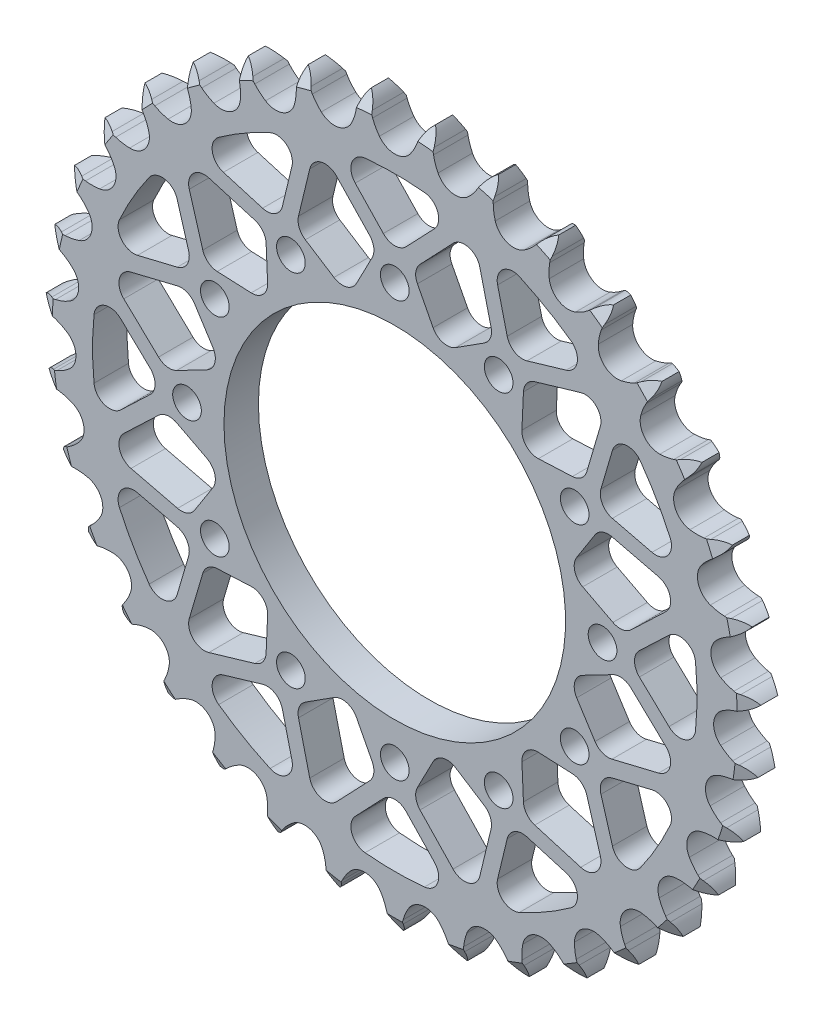
SolidWorks part; units mm, degrees
material "7075-T6 (SN)"
ref_plane "Front Plane" through (0, 0, 0) normal (0, 0, 1) x (1, 0, 0)
ref_plane "Top Plane" through (0, 0, 0) normal (0, 1, 0) x (1, 0, 0)
ref_plane "Right Plane" through (0, 0, 0) normal (1, 0, 0) x (0, 0, -1)
sketch "Work Sketch" plane through (0, 0, 0) normal (0, 0, 1) x (1, 0, 0)
  line L0 (0, 0) -> (0, 160.4542) construction
  line L1 (-112.0919, 70.8395) -> (87.2579, 70.8395) construction
  line L2 (5.0903, 120.8822) -> (5.0903, 112.9699) construction
  line L3 (-12.8497, 74.6356) -> (16.7256, 74.6356) construction
  line L4 (5.0903, 74.6356) -> (-6.074, 66.3097) construction
  line L5 (5.0903, 74.6356) -> (-4.641, 71.0332) construction
  line L6 (-4.641, 71.0332) -> (-6.9559, 77.2865)
  line L7 (-11.5114, 69.8433) -> (-7.1525, 69.8433) construction
  line L8 (-11.0678, 124.7602) -> (-11.0678, 110.2345) construction
  line L9 (0, 0) -> (-3.8324, 42.5811) construction
  circle A0 centre (0, 0) radius 70.8395
  circle A1 centre (0, 70.8395) radius 4.0088
  arc A2 (-4.641, 71.0332) -> (-3.2136, 68.4429) centre (5.0682, 74.6949) ccw
  circle A3 centre (-11.0678, 69.8433) radius 6.4401
  point P23 (-3.2136, 68.4429)
  dimension "D1" = 141.6789
  dimension "D8" = 10.3767
  dimension "D2" = 8.0177
  dimension "D3" = 5.0903
  dimension "D4" = 3.7962
  dimension "D5" = 36.714
  dimension "D6" = 16.4
  dimension "D7" = 10.3767
  dimension "D9" = 0.9961
  dimension "D10" = 11.0678
  dimension "D11" = 5.143
sketch "Teeth Sketch" plane through (0, 0, 0) normal (0, 0, 1) x (1, 0, 0)
  line L0 (5.0282, 72.0792) -> (4.641, 71.0332)
  line L1 (-8.3399, 92.6643) -> (-5.3292, 59.2127) construction
  line L2 (0, 0) -> (-12.1309, 132.2) construction
  line L3 (7.9229, 71.8186) -> (8.1171, 70.7203)
  line L4 (17927.8618, -199194.8588) -> (-17931.6941, 199237.4399) construction
  line L5 (0, 146.3285) -> (0, 56.9858) construction
  line L6 (17.8176, 70.023) -> (17.2498, 69.063)
  line L7 (0, -200000) -> (0, 200160.4542) construction
  line L8 (20.6192, 69.2498) -> (20.6142, 68.1345)
  line L9 (-4.641, 71.0332) -> (-6.9559, 77.2865) construction
  line L10 (43.6371, 57.589) -> (43.2405, 56.5465)
  line L11 (-5.0282, 72.0792) -> (-4.641, 71.0332)
  line L12 (30.0344, 65.7163) -> (29.3043, 64.873)
  line L13 (32.6529, 64.4552) -> (32.4488, 63.3587)
  line L14 (41.2858, 59.2973) -> (40.4169, 58.598)
  line L15 (51.2103, 50.9725) -> (50.2305, 50.4396)
  line L16 (53.2187, 48.8718) -> (52.6424, 47.9169)
  line L17 (59.4888, 41.0094) -> (58.4296, 40.66)
  line L18 (61.0899, 38.5838) -> (60.3523, 37.7472)
  line L19 (65.8553, 29.7283) -> (64.7507, 29.5736)
  line L20 (66.9976, 27.0558) -> (66.1224, 26.3643)
  line L21 (70.1052, 17.4916) -> (68.9907, 17.5366)
  line L22 (70.7519, 14.6581) -> (69.7673, 14.134)
  line L23 (72.1018, 4.6927) -> (71.0133, 4.9361)
  line L24 (72.2322, 1.7893) -> (71.1699, 1.4494)
  line L25 (71.781, -8.2569) -> (70.7534, -7.8232)
  line L26 (71.3909, -11.137) -> (70.2849, -11.2818)
  line L27 (69.1531, -20.9412) -> (68.2195, -20.331)
  line L28 (68.255, -23.7054) -> (67.141, -23.6503)
  line L29 (64.3026, -32.9525) -> (63.493, -32.1853)
  line L30 (62.9254, -35.5118) -> (61.8391, -35.2587)
  line L31 (57.3853, -43.9046) -> (56.7257, -43.0052)
  line L32 (55.5732, -46.1769) -> (54.5496, -45.7339)
  line L33 (48.6237, -53.4456) -> (48.1352, -52.4428)
  line L34 (46.435, -55.3578) -> (45.5069, -54.7392)
  line L35 (38.2992, -61.2688) -> (37.9976, -60.1949)
  line L36 (35.8042, -62.7594) -> (35.0015, -61.985)
  line L37 (26.7437, -67.1227) -> (26.6388, -66.0123)
  line L38 (24.0227, -68.144) -> (23.3712, -67.2387)
  line L39 (14.3287, -70.8193) -> (14.4237, -69.708)
  line L40 (11.4691, -71.3383) -> (10.9896, -70.3312)
  line L41 (1.4532, -72.2397) -> (1.7451, -71.1632)
  line L42 (-1.4532, -72.2397) -> (-1.7451, -71.1632)
  line L43 (-11.4691, -71.3383) -> (-10.9896, -70.3312)
  line L44 (-14.3287, -70.8193) -> (-14.4237, -69.708)
  line L45 (-24.0227, -68.144) -> (-23.3712, -67.2387)
  line L46 (-26.7437, -67.1227) -> (-26.6388, -66.0123)
  line L47 (-35.8042, -62.7594) -> (-35.0015, -61.985)
  line L48 (-38.2992, -61.2688) -> (-37.9976, -60.1949)
  line L49 (-46.435, -55.3578) -> (-45.5069, -54.7392)
  line L50 (-48.6237, -53.4456) -> (-48.1352, -52.4428)
  line L51 (-55.5732, -46.1769) -> (-54.5496, -45.7339)
  line L52 (-57.3853, -43.9046) -> (-56.7257, -43.0052)
  line L53 (-62.9254, -35.5118) -> (-61.8391, -35.2587)
  line L54 (-64.3026, -32.9525) -> (-63.493, -32.1853)
  line L55 (-68.255, -23.7054) -> (-67.141, -23.6503)
  line L56 (-69.1531, -20.9412) -> (-68.2195, -20.331)
  line L57 (-71.3909, -11.137) -> (-70.2849, -11.2818)
  line L58 (-71.781, -8.2569) -> (-70.7534, -7.8232)
  line L59 (-72.2322, 1.7893) -> (-71.1699, 1.4494)
  line L60 (-72.1018, 4.6927) -> (-71.0133, 4.9361)
  line L61 (-70.7519, 14.6581) -> (-69.7673, 14.134)
  line L62 (-70.1052, 17.4916) -> (-68.9907, 17.5366)
  line L63 (-66.9976, 27.0558) -> (-66.1224, 26.3643)
  line L64 (-65.8553, 29.7283) -> (-64.7507, 29.5736)
  line L65 (-61.0899, 38.5838) -> (-60.3523, 37.7472)
  line L66 (-59.4888, 41.0094) -> (-58.4296, 40.66)
  line L67 (-53.2187, 48.8718) -> (-52.6424, 47.9169)
  line L68 (-51.2103, 50.9725) -> (-50.2305, 50.4396)
  line L69 (-43.6371, 57.589) -> (-43.2405, 56.5465)
  line L70 (-41.2858, 59.2973) -> (-40.4169, 58.598)
  line L71 (-32.6529, 64.4552) -> (-32.4488, 63.3587)
  line L72 (-30.0344, 65.7163) -> (-29.3043, 64.873)
  line L73 (-20.6192, 69.2498) -> (-20.6142, 68.1345)
  line L74 (-17.8176, 70.023) -> (-17.2498, 69.063)
  line L75 (-7.9229, 71.8186) -> (-8.1171, 70.7203)
  arc A0 (-6.856, 74.7153) -> (-5.0282, 72.0792) centre (-11.0678, 69.8433) cw
  circle A1 centre (-11.0678, 69.8433) radius 6.4401 construction
  arc A2 (-3.2136, 68.4429) -> (-4.641, 71.0332) centre (5.0682, 74.6949) cw
  arc A3 (-4.641, 71.0332) -> (-3.2136, 68.4429) centre (5.0682, 74.6949) ccw construction
  circle A4 centre (0, 70.8395) radius 4.0088 construction
  arc A5 (-3.2136, 68.4429) -> (3.2136, 68.4429) centre (0, 70.8395) ccw
  arc A6 (3.2136, 68.4429) -> (4.641, 71.0332) centre (-5.0682, 74.6949) ccw
  arc A7 (6.856, 74.7153) -> (5.0282, 72.0792) centre (11.0678, 69.8433) ccw
  arc A8 (6.5951, 74.7388) -> (7.9229, 71.8186) centre (1.5811, 70.6972) cw
  arc A9 (9.059, 67.9168) -> (8.1171, 70.7203) centre (18.324, 72.5896) cw
  arc A10 (9.059, 67.9168) -> (15.3829, 66.7692) centre (12.6489, 69.701) ccw
  arc A11 (15.3829, 66.7692) -> (17.2498, 69.063) centre (8.3506, 74.3995) ccw
  arc A12 (20.0867, 72.2905) -> (17.8176, 70.023) centre (23.3609, 66.7447) ccw
  arc A13 (19.8343, 72.3601) -> (20.6192, 69.2498) centre (14.1792, 69.2787) cw
  arc A14 (21.0404, 65.2078) -> (20.6142, 68.1345) centre (30.9909, 68.1512) cw
  arc A15 (21.0404, 65.2078) -> (27.0578, 62.9494) centre (24.8912, 66.3224) ccw
  arc A16 (27.0578, 62.9494) -> (29.3043, 64.873) centre (21.5009, 71.7128) ccw
  arc A17 (32.6719, 67.5421) -> (30.0344, 65.7163) centre (34.9032, 61.5008) ccw
  arc A18 (32.4359, 67.6557) -> (32.6529, 64.4552) centre (26.3215, 65.6336) cw
  arc A19 (32.3456, 60.403) -> (32.4488, 63.3587) centre (42.6617, 61.5223) cw
  arc A20 (32.3456, 60.403) -> (37.863, 57.1065) centre (36.3335, 60.812) ccw
  arc A21 (37.863, 57.1065) -> (40.4169, 58.598) centre (33.9602, 66.7212) ccw
  arc A22 (44.207, 60.6229) -> (41.2858, 59.2973) centre (45.3237, 54.2803) ccw
  arc A23 (43.9951, 60.7768) -> (43.6371, 57.589) centre (37.6178, 59.8789) cw
  arc A24 (42.6112, 53.6567) -> (43.2405, 56.5465) centre (52.9614, 52.9161) cw
  arc A25 (42.6112, 53.6567) -> (47.4513, 49.428) centre (46.608, 53.3472) ccw
  arc A26 (47.4513, 49.428) -> (50.2305, 50.4396) centre (45.328, 59.5852) ccw
  arc A27 (54.3212, 51.7552) -> (51.2103, 50.9725) centre (54.2875, 45.3151) ccw
  arc A28 (54.1402, 51.9445) -> (53.2187, 48.8718) centre (47.7051, 52.1997) cw
  arc A29 (51.5072, 45.1859) -> (52.6424, 47.9169) centre (61.5588, 42.6091) cw
  arc A30 (51.5072, 45.1859) -> (55.5144, 40.161) centre (55.3845, 44.1677) ccw
  arc A31 (55.5144, 40.161) -> (58.4296, 40.66) centre (55.2389, 50.534) ccw
  arc A32 (62.6894, 41.224) -> (59.4888, 41.0094) centre (61.5064, 34.8935) ccw
  arc A33 (62.5452, 41.4426) -> (61.0899, 38.5838) centre (56.2591, 42.8428) cw
  arc A34 (58.7477, 35.2628) -> (60.3523, 37.7472) centre (68.1777, 30.9326) cw
  arc A35 (58.7477, 35.2628) -> (61.7933, 29.6031) centre (62.3809, 33.5686) ccw
  arc A36 (61.7933, 29.6031) -> (64.7507, 29.5736) centre (63.3744, 39.8586) ccw
  arc A37 (69.0428, 29.3679) -> (65.8553, 29.7283) centre (66.7484, 23.3503) ccw
  arc A38 (68.9399, 29.6087) -> (66.9976, 27.0558) centre (63.0048, 32.1088) cw
  arc A39 (64.1, 24.2063) -> (66.1224, 26.3643) centre (72.6052, 18.2619) cw
  arc A40 (64.1, 24.2063) -> (66.0861, 18.0937) centre (67.3723, 21.8906) ccw
  arc A41 (66.0861, 18.0937) -> (68.9907, 17.5366) centre (69.4729, 27.9021) ccw
  arc A42 (73.1771, 16.5679) -> (70.1052, 17.4916) centre (69.8451, 11.0567) ccw
  arc A43 (73.1188, 16.8232) -> (70.7519, 14.6581) centre (67.7256, 20.3429) cw
  arc A44 (67.3921, 12.3718) -> (69.7673, 14.134) centre (74.6992, 5.0042) cw
  arc A45 (67.3921, 12.3718) -> (68.2548, 6.0028) centre (70.1983, 9.509) ccw
  arc A46 (68.2548, 6.0028) -> (71.0133, 4.9361) centre (73.3386, 15.0489) ccw
  arc A47 (74.9595, 3.2354) -> (72.1018, 4.6927) centre (70.6969, -1.5923) ccw
  arc A48 (74.9477, 3.497) -> (72.2322, 1.7893) centre (70.2696, 7.9231) cw
  arc A49 (68.5181, 0.1397) -> (71.1699, 1.4494) centre (74.3923, -8.4143) cw
  arc A50 (68.5181, 0.1397) -> (68.2298, -6.281) centre (70.7681, -3.1782) ccw
  arc A51 (68.2298, -6.281) -> (70.7534, -7.8232) centre (74.8471, 1.7119) ccw
  arc A52 (74.3325, -10.2012) -> (71.781, -8.2569) centre (69.2765, -14.1901) ccw
  arc A53 (74.3677, -9.9416) -> (71.3909, -11.137) centre (70.555, -4.7513) cw
  arc A54 (67.442, -12.097) -> (70.2849, -11.2818) centre (71.6944, -21.5623) cw
  arc A55 (67.442, -12.097) -> (66.0118, -18.363) centre (69.0634, -15.7633) ccw
  arc A56 (66.0118, -18.363) -> (68.2195, -20.331) centre (73.9499, -11.6801) ccw
  arc A57 (71.3165, -23.3098) -> (69.1531, -20.9412) centre (65.6294, -26.3319) ccw
  arc A58 (71.3974, -23.0607) -> (68.255, -23.7054) centre (68.5728, -17.2731) cw
  arc A59 (64.1981, -23.9448) -> (67.141, -23.6503) centre (66.6921, -34.0173) cw
  arc A60 (64.1981, -23.9448) -> (61.6721, -29.8547) centre (65.1388, -27.8417) ccw
  arc A61 (61.6721, -29.8547) -> (63.493, -32.1853) centre (70.676, -24.6966) ccw
  arc A62 (66.0083, -35.6693) -> (64.3026, -32.9525) centre (59.873, -37.6273) ccw
  arc A63 (66.1324, -35.4386) -> (62.9254, -35.5118) centre (64.3866, -29.2396) cw
  arc A64 (58.8909, -35.023) -> (61.8391, -35.2587) centre (59.5463, -45.379) cw
  arc A65 (58.8909, -35.023) -> (55.3502, -40.3869) centre (59.1207, -39.0252) ccw
  arc A66 (55.3502, -40.3869) -> (56.7257, -43.0052) centre (65.1304, -36.9194) ccw
  arc A67 (58.5785, -46.8823) -> (57.3853, -43.9046) centre (52.1922, -47.7133) ccw
  arc A68 (58.7418, -46.6775) -> (55.5732, -46.1769) centre (58.1309, -40.2664) cw
  arc A69 (51.6909, -44.9755) -> (54.5496, -45.7339) centre (50.4867, -55.2821) cw
  arc A70 (51.6909, -44.9755) -> (47.2494, -49.6211) centre (51.2024, -48.9545) ccw
  arc A71 (47.2494, -49.6211) -> (48.1352, -52.4428) centre (57.4915, -47.9556) ccw
  arc A72 (49.266, -56.5885) -> (48.6237, -53.4456) centre (42.8339, -56.2658) ccw
  arc A73 (49.4632, -56.4161) -> (46.435, -55.3578) centre (50.0069, -49.999) cw
  arc A74 (42.8296, -53.4825) -> (45.5069, -54.7392) centre (39.8043, -63.4085) cw
  arc A75 (42.8296, -53.4825) -> (37.6299, -57.2603) centre (41.6384, -57.3103) ccw
  arc A76 (37.6299, -57.2603) -> (37.9976, -60.1949) centre (48.0048, -57.4505) ccw
  arc A77 (38.37, -64.4758) -> (38.2992, -61.2688) centre (32.0989, -63.0099) ccw
  arc A78 (38.5948, -64.3415) -> (35.8042, -62.7594) centre (40.2756, -58.1246) cw
  arc A79 (32.5916, -60.2706) -> (35.0015, -61.985) centre (27.8426, -69.4968) cw
  arc A80 (32.5916, -60.2706) -> (26.8009, -63.0592) centre (30.7361, -63.8241) ccw
  arc A81 (26.8009, -63.0592) -> (26.6388, -66.0123) centre (36.9752, -65.0988) ccw
  arc A82 (26.2407, -70.2909) -> (26.7437, -67.1227) centre (20.3322, -67.7288) ccw
  arc A83 (26.4859, -70.1989) -> (24.0227, -68.144) centre (29.2498, -64.382) cw
  arc A84 (21.3061, -65.1215) -> (23.3712, -67.2387) centre (14.9861, -73.3515) cw
  arc A85 (21.3061, -65.1215) -> (15.1105, -66.8313) centre (18.8459, -68.2866) ccw
  arc A86 (15.1105, -66.8313) -> (14.4237, -69.708) centre (24.7571, -70.6548) ccw
  arc A87 (13.2681, -73.8468) -> (14.3287, -70.8193) centre (7.912, -70.2708) ccw
  arc A88 (13.5258, -73.8) -> (11.4691, -71.3383) centre (17.2839, -68.5701) cw
  arc A89 (9.3358, -67.8793) -> (10.9896, -70.3312) centre (1.6478, -74.8485) cw
  arc A90 (9.3358, -67.8793) -> (2.9345, -68.4554) centre (6.35, -70.5543) ccw
  arc A91 (2.9345, -68.4554) -> (1.7451, -71.1632) centre (11.7434, -73.9399) ccw
  arc A92 (-0.131, -75.0291) -> (1.4532, -72.2397) centre (-4.7625, -70.5543) ccw
  arc A93 (0.131, -75.0291) -> (-1.4532, -72.2397) centre (4.7625, -70.5543) cw
  arc A94 (-2.9345, -68.4554) -> (-1.7451, -71.1632) centre (-11.7434, -73.9399) cw
  arc A95 (-2.9345, -68.4554) -> (-9.3358, -67.8793) centre (-6.35, -70.5543) ccw
  arc A96 (-9.3358, -67.8793) -> (-10.9896, -70.3312) centre (-1.6478, -74.8485) ccw
  arc A97 (-13.5258, -73.8) -> (-11.4691, -71.3383) centre (-17.2839, -68.5701) ccw
  arc A98 (-13.2681, -73.8468) -> (-14.3287, -70.8193) centre (-7.912, -70.2708) cw
  arc A99 (-15.1105, -66.8313) -> (-14.4237, -69.708) centre (-24.7571, -70.6548) cw
  arc A100 (-15.1105, -66.8313) -> (-21.3061, -65.1215) centre (-18.8459, -68.2866) ccw
  arc A101 (-21.3061, -65.1215) -> (-23.3712, -67.2387) centre (-14.9861, -73.3515) ccw
  arc A102 (-26.4859, -70.1989) -> (-24.0227, -68.144) centre (-29.2498, -64.382) ccw
  arc A103 (-26.2407, -70.2909) -> (-26.7437, -67.1227) centre (-20.3322, -67.7288) cw
  arc A104 (-26.8009, -63.0592) -> (-26.6388, -66.0123) centre (-36.9752, -65.0988) cw
  arc A105 (-26.8009, -63.0592) -> (-32.5916, -60.2706) centre (-30.7361, -63.8241) ccw
  arc A106 (-32.5916, -60.2706) -> (-35.0015, -61.985) centre (-27.8426, -69.4968) ccw
  arc A107 (-38.5948, -64.3415) -> (-35.8042, -62.7594) centre (-40.2756, -58.1246) ccw
  arc A108 (-38.37, -64.4758) -> (-38.2992, -61.2688) centre (-32.0989, -63.0099) cw
  arc A109 (-37.6299, -57.2603) -> (-37.9976, -60.1949) centre (-48.0048, -57.4505) cw
  arc A110 (-37.6299, -57.2603) -> (-42.8296, -53.4825) centre (-41.6384, -57.3103) ccw
  arc A111 (-42.8296, -53.4825) -> (-45.5069, -54.7392) centre (-39.8043, -63.4085) ccw
  arc A112 (-49.4632, -56.4161) -> (-46.435, -55.3578) centre (-50.0069, -49.999) ccw
  arc A113 (-49.266, -56.5885) -> (-48.6237, -53.4456) centre (-42.8339, -56.2658) cw
  arc A114 (-47.2494, -49.6211) -> (-48.1352, -52.4428) centre (-57.4915, -47.9556) cw
  arc A115 (-47.2494, -49.6211) -> (-51.6909, -44.9755) centre (-51.2024, -48.9545) ccw
  arc A116 (-51.6909, -44.9755) -> (-54.5496, -45.7339) centre (-50.4867, -55.2821) ccw
  arc A117 (-58.7418, -46.6775) -> (-55.5732, -46.1769) centre (-58.1309, -40.2664) ccw
  arc A118 (-58.5785, -46.8823) -> (-57.3853, -43.9046) centre (-52.1922, -47.7133) cw
  arc A119 (-55.3502, -40.3869) -> (-56.7257, -43.0052) centre (-65.1304, -36.9194) cw
  arc A120 (-55.3502, -40.3869) -> (-58.8909, -35.023) centre (-59.1207, -39.0252) ccw
  arc A121 (-58.8909, -35.023) -> (-61.8391, -35.2587) centre (-59.5463, -45.379) ccw
  arc A122 (-66.1324, -35.4386) -> (-62.9254, -35.5118) centre (-64.3866, -29.2396) ccw
  arc A123 (-66.0083, -35.6693) -> (-64.3026, -32.9525) centre (-59.873, -37.6273) cw
  arc A124 (-61.6721, -29.8547) -> (-63.493, -32.1853) centre (-70.676, -24.6966) cw
  arc A125 (-61.6721, -29.8547) -> (-64.1981, -23.9448) centre (-65.1388, -27.8417) ccw
  arc A126 (-64.1981, -23.9448) -> (-67.141, -23.6503) centre (-66.6921, -34.0173) ccw
  arc A127 (-71.3974, -23.0607) -> (-68.255, -23.7054) centre (-68.5728, -17.2731) ccw
  arc A128 (-71.3165, -23.3098) -> (-69.1531, -20.9412) centre (-65.6294, -26.3319) cw
  arc A129 (-66.0118, -18.363) -> (-68.2195, -20.331) centre (-73.9499, -11.6801) cw
  arc A130 (-66.0118, -18.363) -> (-67.442, -12.097) centre (-69.0634, -15.7633) ccw
  arc A131 (-67.442, -12.097) -> (-70.2849, -11.2818) centre (-71.6944, -21.5623) ccw
  arc A132 (-74.3677, -9.9416) -> (-71.3909, -11.137) centre (-70.555, -4.7513) ccw
  arc A133 (-74.3325, -10.2012) -> (-71.781, -8.2569) centre (-69.2765, -14.1901) cw
  arc A134 (-68.2298, -6.281) -> (-70.7534, -7.8232) centre (-74.8471, 1.7119) cw
  arc A135 (-68.2298, -6.281) -> (-68.5181, 0.1397) centre (-70.7681, -3.1782) ccw
  arc A136 (-68.5181, 0.1397) -> (-71.1699, 1.4494) centre (-74.3923, -8.4143) ccw
  arc A137 (-74.9477, 3.497) -> (-72.2322, 1.7893) centre (-70.2696, 7.9231) ccw
  arc A138 (-74.9595, 3.2354) -> (-72.1018, 4.6927) centre (-70.6969, -1.5923) cw
  arc A139 (-68.2548, 6.0028) -> (-71.0133, 4.9361) centre (-73.3386, 15.0489) cw
  arc A140 (-68.2548, 6.0028) -> (-67.3921, 12.3718) centre (-70.1983, 9.509) ccw
  arc A141 (-67.3921, 12.3718) -> (-69.7673, 14.134) centre (-74.6992, 5.0042) ccw
  arc A142 (-73.1188, 16.8232) -> (-70.7519, 14.6581) centre (-67.7256, 20.3429) ccw
  arc A143 (-73.1771, 16.5679) -> (-70.1052, 17.4916) centre (-69.8451, 11.0567) cw
  arc A144 (-66.0861, 18.0937) -> (-68.9907, 17.5366) centre (-69.4729, 27.9021) cw
  arc A145 (-66.0861, 18.0937) -> (-64.1, 24.2063) centre (-67.3723, 21.8906) ccw
  arc A146 (-64.1, 24.2063) -> (-66.1224, 26.3643) centre (-72.6052, 18.2619) ccw
  arc A147 (-68.9399, 29.6087) -> (-66.9976, 27.0558) centre (-63.0048, 32.1088) ccw
  arc A148 (-69.0428, 29.3679) -> (-65.8553, 29.7283) centre (-66.7484, 23.3503) cw
  arc A149 (-61.7933, 29.6031) -> (-64.7507, 29.5736) centre (-63.3744, 39.8586) cw
  arc A150 (-61.7933, 29.6031) -> (-58.7477, 35.2628) centre (-62.3809, 33.5686) ccw
  arc A151 (-58.7477, 35.2628) -> (-60.3523, 37.7472) centre (-68.1777, 30.9326) ccw
  arc A152 (-62.5452, 41.4426) -> (-61.0899, 38.5838) centre (-56.2591, 42.8428) ccw
  arc A153 (-62.6894, 41.224) -> (-59.4888, 41.0094) centre (-61.5064, 34.8935) cw
  arc A154 (-55.5144, 40.161) -> (-58.4296, 40.66) centre (-55.2389, 50.534) cw
  arc A155 (-55.5144, 40.161) -> (-51.5072, 45.1859) centre (-55.3845, 44.1677) ccw
  arc A156 (-51.5072, 45.1859) -> (-52.6424, 47.9169) centre (-61.5588, 42.6091) ccw
  arc A157 (-54.1402, 51.9445) -> (-53.2187, 48.8718) centre (-47.7051, 52.1997) ccw
  arc A158 (-54.3212, 51.7552) -> (-51.2103, 50.9725) centre (-54.2875, 45.3151) cw
  arc A159 (-47.4513, 49.428) -> (-50.2305, 50.4396) centre (-45.328, 59.5852) cw
  arc A160 (-47.4513, 49.428) -> (-42.6112, 53.6567) centre (-46.608, 53.3472) ccw
  arc A161 (-42.6112, 53.6567) -> (-43.2405, 56.5465) centre (-52.9614, 52.9161) ccw
  arc A162 (-43.9951, 60.7768) -> (-43.6371, 57.589) centre (-37.6178, 59.8789) ccw
  arc A163 (-44.207, 60.6229) -> (-41.2858, 59.2973) centre (-45.3237, 54.2803) cw
  arc A164 (-37.863, 57.1065) -> (-40.4169, 58.598) centre (-33.9602, 66.7212) cw
  arc A165 (-37.863, 57.1065) -> (-32.3456, 60.403) centre (-36.3335, 60.812) ccw
  arc A166 (-32.3456, 60.403) -> (-32.4488, 63.3587) centre (-42.6617, 61.5223) ccw
  arc A167 (-32.4359, 67.6557) -> (-32.6529, 64.4552) centre (-26.3215, 65.6336) ccw
  arc A168 (-32.6719, 67.5421) -> (-30.0344, 65.7163) centre (-34.9032, 61.5008) cw
  arc A169 (-27.0578, 62.9494) -> (-29.3043, 64.873) centre (-21.5009, 71.7128) cw
  arc A170 (-27.0578, 62.9494) -> (-21.0404, 65.2078) centre (-24.8912, 66.3224) ccw
  arc A171 (-21.0404, 65.2078) -> (-20.6142, 68.1345) centre (-30.9909, 68.1512) ccw
  arc A172 (-19.8343, 72.3601) -> (-20.6192, 69.2498) centre (-14.1792, 69.2787) ccw
  arc A173 (-20.0867, 72.2905) -> (-17.8176, 70.023) centre (-23.3609, 66.7447) cw
  arc A174 (-15.3829, 66.7692) -> (-17.2498, 69.063) centre (-8.3506, 74.3995) cw
  arc A175 (-15.3829, 66.7692) -> (-9.059, 67.9168) centre (-12.6489, 69.701) ccw
  arc A176 (-9.059, 67.9168) -> (-8.1171, 70.7203) centre (-18.324, 72.5896) ccw
  arc A177 (-6.5951, 74.7388) -> (-7.9229, 71.8186) centre (-1.5811, 70.6972) ccw
  point P77 (0, 0)
  dimension "D1" = 5.143
  dimension "D2" = 5.243
  dimension "D3" = 35
extrude "Extrusion" add sketch "Teeth Sketch" along normal blind 7.2136 contours A0 region at (0, 0, 0)
sketch "Sketch1" plane through (0, 0, 0) normal (0, 0, -1) x (-1, 0, 0)
  circle A0 centre (0, 0) radius 78.9443
  circle A1 centre (0, 0) radius 35.7643
  dimension "D1" = 43.18
extrude "Cut-Extrude" cut sketch "Sketch1" against normal through all both and the other way through all contours A1
ref_axis "Axis2" through (0, 0, -0.3607) along (0, 0, 1)
ref_axis "Axis1" [suppressed] through (0, 0, 7.2136) along (0, 0, -1)
ref_plane "Sprocket Center Plane" through (0, 0, 3.6068) normal (0, 0, 1) x (1, 0, 0)
sketch "Pitch Circle" plane through (0, 0, 3.6068) normal (0, 0, -1) x (-1, 0, 0)
  circle A0 centre (0, 0) radius 82.9531 construction
  dimension "D1" = 165.9063
sketch "Chain Pitch Circle" plane through (0, 0, 0) normal (0, 0, -1) x (-1, 0, 0)
  circle A0 centre (0, 0) radius 82.9531 construction
  dimension "D1" = 165.9063
ref_plane "Center Plane" through (0, 0, 3.6068) normal (0, 0, 1) x (1, 0, 0)
hole_wizard "Ø6.0mm Dowel Hole1" positions "Sketch7" profile "Sketch8" hole size "Ø6.0" standard "ANSI Metric" end condition through all
sketch "Sketch7" plane through (0, 0, 7.2136) normal (0, 0, 1) x (1, 0, 0)
  point P0 (-43.5, 0)
  dimension "D1" = 43.5
sketch "Sketch8" plane through (-43.5, 0, 7.2136) normal (1, 0, 0) x (0, -1, 0)
  line L0 (0, 0) -> (0, 7.2136)
  line L1 (0, 7.2136) -> (3, 7.2136)
  line L2 (3, 7.2136) -> (3, 0)
  line L5 (3, 0) -> (0, 0)
  line L11 (0, -6.35) -> (0, 107.95) construction
  dimension "Thru Hole Dia." = 6
  dimension "Thru Hole Depth" = 7.2136
pattern_circular "CirPattern1" count 12 over 360 about axis through (0, 0, 7.2136) along (0, 0, -1) of "Ø6.0mm Dowel Hole1" reverse direction yes
ref_plane "Plane1" through (0, 0, 3.6068) normal (0, 0, -1) x (-1, 0, 0)
sketch "Sketch9" plane through (0, 0, 0) normal (0, 0, 1) x (1, 0, 0)
  line L0 (-43.5, 0) -> (-63.2746, 0) construction
  line L1 (-61.9966, 12.6533) -> (-48.707, 0)
  line L2 (-61.9966, -12.6533) -> (-48.707, 0)
  line L11 (-43.5, 0) -> (-37.6721, 21.75) construction
  line L13 (-61.1186, 16.3767) -> (-36.1404, 9.6838) construction
  line L18 (-43.1887, 20.7127) -> (-36.1404, 9.6838)
  line L19 (-47.7589, 3.6566) -> (-36.1404, 9.6838)
  line L20 (-43.1887, 20.7127) -> (-61.1186, 16.3767)
  line L21 (-47.7589, 3.6566) -> (-61.1186, 16.3767)
  circle A0 centre (0, 0) radius 66.8306 construction
  arc A1 (-15.3829, 66.7692) -> (-9.059, 67.9168) centre (-12.6489, 69.701) ccw construction
  circle A2 centre (-43.5, 0) radius 3 construction
  circle A3 centre (-43.5, 0) radius 5.207
  circle A4 centre (-37.6721, 21.75) radius 3 construction
  circle A6 centre (-37.6721, 21.75) radius 5.207
  circle A196 centre (0, 0) radius 63.2746
  circle A197 centre (0, 0) radius 35.7643 construction
  circle A198 centre (0, 0) radius 35.7643
  circle A199 centre (0, 0) radius 37.4153 construction
  point P17 (-40.5861, 10.875)
  dimension "D1" = 3.556
  dimension "D2" = 1.651
  dimension "D3" = 10.414
  dimension "D4" = 3.302
extrude "Cut-Extrude2" cut sketch "Sketch9" along normal through all contours L1 A196 L2 | L21 L19 L18 L20 region at (-58.1293, 0, 0) region at (-47.5776, 12.7484, 0)
fillet "Fillet2" radius 3.302 7 edges at (-61.1186, 16.3767, 3.6068) (-36.1404, 9.6838, 3.6068) (-47.7589, 3.6566, 3.6068) (-43.1887, 20.7127, 3.6068) (-61.9966, -12.6533, 3.6068) (-48.707, 0, 3.6068) (-61.9966, 12.6533, 3.6068)
pattern_circular "CirPattern3" count 12 over 360 about axis through (0, 0, 7.2136) along (0, 0, -1) of "Cut-Extrude2", "Fillet2"
sketch "Sketch14" plane through (0, 0, 7.2136) normal (0, 0, 1) x (1, 0, 0)
  line L0 (-45.6677, -4.7414) -> (-39.3483, -8.0197) construction
  line L1 (-38.2956, 5.9905) -> (-37.9766, 6.1559)
  line L2 (-43.5, 0) -> (-38.293, 0) construction
  line L3 (-38.2956, -5.9905) -> (-37.9766, -6.1559)
  line L4 (-30.1697, 24.3357) -> (-29.8108, 24.3195)
  line L5 (-36.1602, 13.9599) -> (-35.9667, 13.6571)
  line L6 (-13.9599, 36.1602) -> (-13.6571, 35.9667)
  line L7 (-24.3357, 30.1697) -> (-24.3195, 29.8108)
  line L8 (5.9905, 38.2956) -> (6.1559, 37.9766)
  line L9 (-5.9905, 38.2956) -> (-6.1559, 37.9766)
  line L10 (24.3357, 30.1697) -> (24.3195, 29.8108)
  line L11 (13.9599, 36.1602) -> (13.6571, 35.9667)
  line L12 (36.1602, 13.9599) -> (35.9667, 13.6571)
  line L13 (30.1697, 24.3357) -> (29.8108, 24.3195)
  line L14 (38.2956, -5.9905) -> (37.9766, -6.1559)
  line L15 (38.2956, 5.9905) -> (37.9766, 6.1559)
  line L16 (30.1697, -24.3357) -> (29.8108, -24.3195)
  line L17 (36.1602, -13.9599) -> (35.9667, -13.6571)
  line L18 (13.9599, -36.1602) -> (13.6571, -35.9667)
  line L19 (24.3357, -30.1697) -> (24.3195, -29.8108)
  line L20 (-5.9905, -38.2956) -> (-6.1559, -37.9766)
  line L21 (5.9905, -38.2956) -> (6.1559, -37.9766)
  line L22 (-24.3357, -30.1697) -> (-24.3195, -29.8108)
  line L23 (-13.9599, -36.1602) -> (-13.6571, -35.9667)
  line L24 (-36.1602, -13.9599) -> (-35.9667, -13.6571)
  line L25 (-30.1697, -24.3357) -> (-29.8108, -24.3195)
  arc A0 (-39.0014, -2.6222) -> (-39.0014, 2.6222) centre (-43.5, 0) ccw
  circle A1 centre (0, 0) radius 35.7643 construction
  arc A2 (-37.9766, -6.1559) -> (-39.0014, -2.6222) centre (-36.807, -3.9013) cw
  arc A3 (-38.2956, 5.9905) -> (-36.1602, 13.9599) centre (-40.8688, 10.9508) ccw
  arc A4 (-38.2956, 5.9905) -> (-36.1602, 13.9599) centre (-40.8688, 10.9508) ccw
  arc A5 (-37.9766, 6.1559) -> (-39.0014, 2.6222) centre (-36.807, 3.9013) ccw
  circle A6 centre (0, 0) radius 35.7643
  arc A7 (-30.1697, 24.3357) -> (-24.3357, 30.1697) centre (-29.918, 29.918) ccw
  arc A8 (-29.8108, 24.3195) -> (-32.4651, 21.7716) centre (-29.9252, 21.7821) ccw
  arc A9 (-35.0873, 17.2299) -> (-32.4651, 21.7716) centre (-37.6721, 21.75) ccw
  arc A10 (-35.9667, 13.6571) -> (-35.0873, 17.2299) centre (-33.8264, 15.0249) cw
  arc A11 (-13.9599, 36.1602) -> (-5.9905, 38.2956) centre (-10.9508, 40.8688) ccw
  arc A12 (-13.6571, 35.9667) -> (-17.2299, 35.0873) centre (-15.0249, 33.8264) ccw
  arc A13 (-21.7716, 32.4651) -> (-17.2299, 35.0873) centre (-21.75, 37.6721) ccw
  arc A14 (-24.3195, 29.8108) -> (-21.7716, 32.4651) centre (-21.7821, 29.9252) cw
  arc A15 (5.9905, 38.2956) -> (13.9599, 36.1602) centre (10.9508, 40.8688) ccw
  arc A16 (6.1559, 37.9766) -> (2.6222, 39.0014) centre (3.9013, 36.807) ccw
  arc A17 (-2.6222, 39.0014) -> (2.6222, 39.0014) centre (0, 43.5) ccw
  arc A18 (-6.1559, 37.9766) -> (-2.6222, 39.0014) centre (-3.9013, 36.807) cw
  arc A19 (24.3357, 30.1697) -> (30.1697, 24.3357) centre (29.918, 29.918) ccw
  arc A20 (24.3195, 29.8108) -> (21.7716, 32.4651) centre (21.7821, 29.9252) ccw
  arc A21 (17.2299, 35.0873) -> (21.7716, 32.4651) centre (21.75, 37.6721) ccw
  arc A22 (13.6571, 35.9667) -> (17.2299, 35.0873) centre (15.0249, 33.8264) cw
  arc A23 (36.1602, 13.9599) -> (38.2956, 5.9905) centre (40.8688, 10.9508) ccw
  arc A24 (35.9667, 13.6571) -> (35.0873, 17.2299) centre (33.8264, 15.0249) ccw
  arc A25 (32.4651, 21.7716) -> (35.0873, 17.2299) centre (37.6721, 21.75) ccw
  arc A26 (29.8108, 24.3195) -> (32.4651, 21.7716) centre (29.9252, 21.7821) cw
  arc A27 (38.2956, -5.9905) -> (36.1602, -13.9599) centre (40.8688, -10.9508) ccw
  arc A28 (37.9766, -6.1559) -> (39.0014, -2.6222) centre (36.807, -3.9013) ccw
  arc A29 (39.0014, 2.6222) -> (39.0014, -2.6222) centre (43.5, 0) ccw
  arc A30 (37.9766, 6.1559) -> (39.0014, 2.6222) centre (36.807, 3.9013) cw
  arc A31 (30.1697, -24.3357) -> (24.3357, -30.1697) centre (29.918, -29.918) ccw
  arc A32 (29.8108, -24.3195) -> (32.4651, -21.7716) centre (29.9252, -21.7821) ccw
  arc A33 (35.0873, -17.2299) -> (32.4651, -21.7716) centre (37.6721, -21.75) ccw
  arc A34 (35.9667, -13.6571) -> (35.0873, -17.2299) centre (33.8264, -15.0249) cw
  arc A35 (13.9599, -36.1602) -> (5.9905, -38.2956) centre (10.9508, -40.8688) ccw
  arc A36 (13.6571, -35.9667) -> (17.2299, -35.0873) centre (15.0249, -33.8264) ccw
  arc A37 (21.7716, -32.4651) -> (17.2299, -35.0873) centre (21.75, -37.6721) ccw
  arc A38 (24.3195, -29.8108) -> (21.7716, -32.4651) centre (21.7821, -29.9252) cw
  arc A39 (-5.9905, -38.2956) -> (-13.9599, -36.1602) centre (-10.9508, -40.8688) ccw
  arc A40 (-6.1559, -37.9766) -> (-2.6222, -39.0014) centre (-3.9013, -36.807) ccw
  arc A41 (2.6222, -39.0014) -> (-2.6222, -39.0014) centre (0, -43.5) ccw
  arc A42 (6.1559, -37.9766) -> (2.6222, -39.0014) centre (3.9013, -36.807) cw
  arc A43 (-24.3357, -30.1697) -> (-30.1697, -24.3357) centre (-29.918, -29.918) ccw
  arc A44 (-24.3195, -29.8108) -> (-21.7716, -32.4651) centre (-21.7821, -29.9252) ccw
  arc A45 (-17.2299, -35.0873) -> (-21.7716, -32.4651) centre (-21.75, -37.6721) ccw
  arc A46 (-13.6571, -35.9667) -> (-17.2299, -35.0873) centre (-15.0249, -33.8264) cw
  arc A47 (-36.1602, -13.9599) -> (-38.2956, -5.9905) centre (-40.8688, -10.9508) ccw
  arc A48 (-35.9667, -13.6571) -> (-35.0873, -17.2299) centre (-33.8264, -15.0249) ccw
  arc A49 (-32.4651, -21.7716) -> (-35.0873, -17.2299) centre (-37.6721, -21.75) ccw
  arc A50 (-29.8108, -24.3195) -> (-32.4651, -21.7716) centre (-29.9252, -21.7821) cw
  point P10 (-41.0188, -4.5778)
  point P16 (-41.0188, 4.5778)
  point P144 (0, 0)
  dimension "D2" = 2.54
  dimension "D1" = 2.286
  dimension "D3" = 12
extrude "Cut-Extrude7" [suppressed] cut sketch "Sketch14" against normal through all
sketch "Sketch15" plane through (0, 0, 0) normal (0, 0, -1) x (-1, 0, 0)
  line L9 (-30.8009, 49.3753) -> (-28.037, 48.5615)
  line L10 (-28.037, 48.5615) -> (-27.3598, 51.362)
  line L11 (-48.5615, 28.037) -> (-49.3753, 30.8009)
  line L12 (-51.362, 27.3598) -> (-48.5615, 28.037)
  line L13 (-48.5615, 28.037) -> (-49.3753, 30.8009)
  line L14 (-51.362, 27.3598) -> (-48.5615, 28.037)
  line L15 (-46.8809, 9.8349) -> (-43.4148, 11.633)
  line L16 (-50.8663, 13.6296) -> (-46.8809, 9.8349)
  line L17 (-45.5175, 14.9231) -> (-50.8663, 13.6296)
  line L18 (-43.4148, 11.633) -> (-45.5175, 14.9231)
  line L19 (-46.8809, 9.8349) -> (-43.4148, 11.633)
  line L20 (-50.8663, 13.6296) -> (-46.8809, 9.8349)
  line L21 (-45.5175, 14.9231) -> (-50.8663, 13.6296)
  line L22 (-43.4148, 11.633) -> (-45.5175, 14.9231)
  line L23 (-37.2367, 37.2367) -> (-35.6825, 31.9577)
  line L24 (-35.6825, 31.9577) -> (-31.7819, 31.7819)
  line L25 (-31.7819, 31.7819) -> (-31.9577, 35.6825)
  line L26 (-31.9577, 35.6825) -> (-37.2367, 37.2367)
  line L27 (-1.9867, 58.1607) -> (0, 56.074)
  line L28 (0, 56.074) -> (1.9867, 58.1607)
  line L29 (-13.6296, 50.8663) -> (-14.9231, 45.5175)
  line L30 (-14.9231, 45.5175) -> (-11.633, 43.4148)
  line L31 (-11.633, 43.4148) -> (-9.8349, 46.8809)
  line L32 (-9.8349, 46.8809) -> (-13.6296, 50.8663)
  line L33 (27.3598, 51.362) -> (28.037, 48.5615)
  line L34 (28.037, 48.5615) -> (30.8009, 49.3753)
  line L35 (13.6296, 50.8663) -> (9.8349, 46.8809)
  line L36 (9.8349, 46.8809) -> (11.633, 43.4148)
  line L37 (11.633, 43.4148) -> (14.9231, 45.5175)
  line L38 (14.9231, 45.5175) -> (13.6296, 50.8663)
  line L39 (49.3753, 30.8009) -> (48.5615, 28.037)
  line L40 (48.5615, 28.037) -> (51.362, 27.3598)
  line L41 (37.2367, 37.2367) -> (31.9577, 35.6825)
  line L42 (31.9577, 35.6825) -> (31.7819, 31.7819)
  line L43 (31.7819, 31.7819) -> (35.6825, 31.9577)
  line L44 (35.6825, 31.9577) -> (37.2367, 37.2367)
  line L45 (58.1607, 1.9867) -> (56.074, 0)
  line L46 (56.074, 0) -> (58.1607, -1.9867)
  line L47 (50.8663, 13.6296) -> (45.5175, 14.9231)
  line L48 (45.5175, 14.9231) -> (43.4148, 11.633)
  line L49 (43.4148, 11.633) -> (46.8809, 9.8349)
  line L50 (46.8809, 9.8349) -> (50.8663, 13.6296)
  line L51 (51.362, -27.3598) -> (48.5615, -28.037)
  line L52 (48.5615, -28.037) -> (49.3753, -30.8009)
  line L53 (50.8663, -13.6296) -> (46.8809, -9.8349)
  line L54 (46.8809, -9.8349) -> (43.4148, -11.633)
  line L55 (43.4148, -11.633) -> (45.5175, -14.9231)
  line L56 (45.5175, -14.9231) -> (50.8663, -13.6296)
  line L57 (30.8009, -49.3753) -> (28.037, -48.5615)
  line L58 (28.037, -48.5615) -> (27.3598, -51.362)
  line L59 (37.2367, -37.2367) -> (35.6825, -31.9577)
  line L60 (35.6825, -31.9577) -> (31.7819, -31.7819)
  line L61 (31.7819, -31.7819) -> (31.9577, -35.6825)
  line L62 (31.9577, -35.6825) -> (37.2367, -37.2367)
  line L63 (1.9867, -58.1607) -> (0, -56.074)
  line L64 (0, -56.074) -> (-1.9867, -58.1607)
  line L65 (13.6296, -50.8663) -> (14.9231, -45.5175)
  line L66 (14.9231, -45.5175) -> (11.633, -43.4148)
  line L67 (11.633, -43.4148) -> (9.8349, -46.8809)
  line L68 (9.8349, -46.8809) -> (13.6296, -50.8663)
  line L69 (-27.3598, -51.362) -> (-28.037, -48.5615)
  line L70 (-28.037, -48.5615) -> (-30.8009, -49.3753)
  line L71 (-13.6296, -50.8663) -> (-9.8349, -46.8809)
  line L72 (-9.8349, -46.8809) -> (-11.633, -43.4148)
  line L73 (-11.633, -43.4148) -> (-14.9231, -45.5175)
  line L74 (-14.9231, -45.5175) -> (-13.6296, -50.8663)
  line L75 (-49.3753, -30.8009) -> (-48.5615, -28.037)
  line L76 (-48.5615, -28.037) -> (-51.362, -27.3598)
  line L77 (-37.2367, -37.2367) -> (-31.9577, -35.6825)
  line L78 (-31.9577, -35.6825) -> (-31.7819, -31.7819)
  line L79 (-31.7819, -31.7819) -> (-35.6825, -31.9577)
  line L80 (-35.6825, -31.9577) -> (-37.2367, -37.2367)
  line L81 (-58.1607, -1.9867) -> (-56.074, 0)
  line L82 (-56.074, 0) -> (-58.1607, 1.9867)
  line L83 (-50.8663, -13.6296) -> (-45.5175, -14.9231)
  line L84 (-45.5175, -14.9231) -> (-43.4148, -11.633)
  line L85 (-43.4148, -11.633) -> (-46.8809, -9.8349)
  line L86 (-46.8809, -9.8349) -> (-50.8663, -13.6296)
  circle A13 centre (0, 0) radius 31.6425
  arc A18 (-27.3598, 51.362) -> (-30.8009, 49.3753) centre (0, 0) ccw
  arc A19 (1.9867, 58.1607) -> (-1.9867, 58.1607) centre (0, 0) ccw
  arc A20 (30.8009, 49.3753) -> (27.3598, 51.362) centre (0, 0) ccw
  arc A21 (51.362, 27.3598) -> (49.3753, 30.8009) centre (0, 0) ccw
  arc A22 (-49.3753, 30.8009) -> (-51.362, 27.3598) centre (0, 0) ccw
  arc A23 (-49.3753, 30.8009) -> (-51.362, 27.3598) centre (0, 0) ccw
  arc A24 (58.1607, -1.9867) -> (58.1607, 1.9867) centre (0, 0) ccw
  arc A25 (49.3753, -30.8009) -> (51.362, -27.3598) centre (0, 0) ccw
  arc A26 (27.3598, -51.362) -> (30.8009, -49.3753) centre (0, 0) ccw
  arc A27 (-1.9867, -58.1607) -> (1.9867, -58.1607) centre (0, 0) ccw
  arc A28 (-30.8009, -49.3753) -> (-27.3598, -51.362) centre (0, 0) ccw
  arc A29 (-51.362, -27.3598) -> (-49.3753, -30.8009) centre (0, 0) ccw
  arc A30 (-58.1607, 1.9867) -> (-58.1607, -1.9867) centre (0, 0) ccw
  point P3 (0, 0)
  point P28 (0, 0)
  point P123 (0, 0)
  dimension "D6" = 5.08
  dimension "D7" = 5.08
  dimension "D8" = 12
sketch "Sketch16" plane through (0, 0, 0) normal (0, 0, -1) x (-1, 0, 0)
  line L1 (88.9, 88.9) -> (-88.9, 88.9)
  line L2 (88.9, 88.9) -> (88.9, -88.9)
  line L3 (88.9, -88.9) -> (-88.9, -88.9)
  line L4 (-88.9, 88.9) -> (-88.9, -88.9)
  line L5 (88.9, 88.9) -> (-88.9, -88.9) construction
  line L6 (88.9, -88.9) -> (-88.9, 88.9) construction
  point P0 (0, 0)
  dimension "D1" = 177.8
  dimension "D2" = 177.8
sketch "Sketch17" plane through (0, 0, 0) normal (0, 0, -1) x (-1, 0, 0)
  line L0 (88.9, 88.9) -> (-88.9, -88.9) construction
  line L2 (88.9, -88.9) -> (-88.9, -88.9)
  line L3 (88.9, -88.9) -> (88.9, 88.9)
  line L4 (88.9, 88.9) -> (-88.9, 88.9)
  line L5 (-88.9, -88.9) -> (-88.9, 88.9)
  line L6 (88.9, -88.9) -> (-88.9, 88.9) construction
  line L7 (88.9, 88.9) -> (-88.9, -88.9) construction
  circle A0 centre (0, 0) radius 74.8895
sketch "Sketch18" plane through (0, 0, 0) normal (1, 0, 0) x (0, 0, -1)
  line L0 (-4.4369, -78.3168) -> (-5.3848, -74.8895)
  line L1 (-5.3848, -74.8895) -> (-5.3848, -71.6959)
  line L2 (-5.3848, -71.6959) -> (-7.2136, -71.6959)
  line L3 (-7.2136, -71.6959) -> (-5.3848, -74.8895)
  line L4 (-7.2136, -71.6959) -> (-7.2136, -74.8895)
  line L5 (-7.2136, -74.8895) -> (-5.3848, -74.8895)
  line L6 (-7.2136, -71.6959) -> (-7.2136, -74.8895)
  line L7 (-5.3848, -74.8895) -> (-7.2136, -71.6959)
  dimension "D1" = 3.556
  dimension "D2" = 3.1936
  dimension "D3" = 1.8288
revolve "Cut-Revolve2" cut sketch "Sketch18" angle 360 about axis through (0, 0, -0.3607) along (0, 0, 1) region at (0, -73.825, 6.604)
mirror "Mirror1" about plane through (0, 0, 3.6068) normal (0, 0, -1) of "Cut-Revolve2"
equation "\"P\"= 0.500'//Chain Pitch"
equation "\"N\"= 35'//Number of Teeth"
equation "\"Dr\"= 5 / 16'//Roller Diameter"
equation "\"Ds\"= 1.0005 * \"Dr\" + 0.003'Seating Curve DIameter"
equation "\"R\"= \"Ds\" / 2"
equation "\"A\"= 35 + 60 / \"N\""
equation "\"B\"= 18 - 56 / \"N\""
equation "\"ac\"= 0.8 * \"Dr\""
equation "\"M\"= 0.8 * \"Dr\" * cos ( 35 + 60 / \"N\" )"
equation "\"T\"= 0.8 * \"Dr\" * sin ( 35 + 60 / \"N\" )"
equation "\"E\"= 1.3025 * \"Dr\" + 0.0015"
equation "\"Chordal Length of Arc xy\"= ( 2.605 * \"Dr\" + 0.003 ) * sin ( 9 - 28 / \"N\" )"
equation "\"yz\"= \"Dr\" * ( 1.4 * sin ( 17 - 64 / \"N\" ) - 0.8 * sin ( 18 - 56 / \"N\" ) )"
equation "\"ab\"= 1.4 * \"Dr\""
equation "\"W\"= 1.4 * \"Dr\" * cos ( 180 / \"N\" )"
equation "\"V\"= 1.4 * \"Dr\" * sin ( 180 / \"N\" )"
equation "\"F\"= \"Dr\" * ( 0.8 * cos ( 18 - 56 / \"N\" ) + 1.4 * cos ( 17 - 64 / \"N\" ) - 1.3025 )"
equation "\"H\"= sqr ( \"F\" ^ 2 - ( 1.4 * \"Dr\" - \"P\" / 2 ) ^ 2 )"
equation "\"S\"= \"P\" / 2 * cos ( 180 / \"N\" ) + \"H\" * sin ( 180 / \"N\" )"
equation "\"PD\"= \"P\" / ( sin ( 180 / \"N\" ) )"
equation "\"D1@Work Sketch\" = \"PD\""
equation "\"D3@Work Sketch\" = \"M\""
equation "\"D4@Work Sketch\" = \"T\""
equation "\"D5@Work Sketch\" = \"A\""
equation "\"D6@Work Sketch\" = \"B\""
equation "\"D7@Work Sketch\" = \"E\""
equation "\"D8@Work Sketch\" = \"E\""
equation "\"D9@Work Sketch\" = \"V\""
equation "\"D10@Work Sketch\" = \"W\""
equation "\"D2@Work Sketch\" = \"R\" * 2"
equation "\"D11@Work Sketch\" = 180 / \"N\""
equation "\"D2@Teeth Sketch\" = 180 / \"N\" + 0.1"
equation "\"D3@Teeth Sketch\" = \"N\""
equation "\"Edge Thickness\"=1.7"
equation "\"D1@Sketch1\"=\"Edge Thickness\""
equation "\"InnerRib\"=0.060000"
equation "\"ST\"= 0.284'//Sprocket Thickness"
